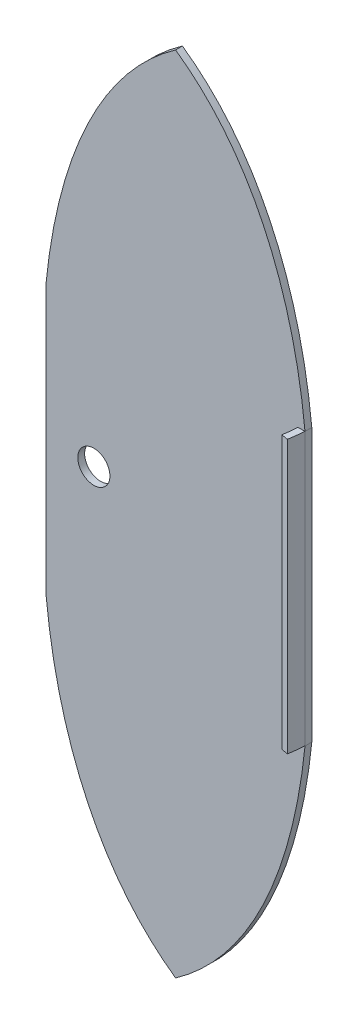
SolidWorks part; units mm, degrees
material "1060 Alloy"
ref_plane "Front Plane" through (0, 0, 0) normal (0, 0, 1) x (1, 0, 0)
ref_plane "Top Plane" through (0, 0, 0) normal (0, 1, 0) x (1, 0, 0)
ref_plane "Right Plane" through (0, 0, 0) normal (1, 0, 0) x (0, 0, -1)
sketch "Sketch1" plane through (0, 0, 0) normal (0, 0, 1) x (1, 0, 0)
  line L2 (0, 0) -> (-130.3555, 0) construction
  line L3 (0, 0) -> (0, -49.0041) construction
  line L4 (-48.26, 0) -> (-48.26, -101.6)
  line L7 (48.26, 0) -> (48.26, -101.6)
  line L8 (0, -50.8) -> (-48.26, -50.8) construction
  line L9 (48.26, 0) -> (45.72, 0)
  line L10 (45.72, 0) -> (45.72, -101.6)
  line L11 (45.72, -101.6) -> (48.26, -101.6)
  circle A0 centre (-30.48, -50.8) radius 5.9944
  spline S0 degree 3 poles (-48.26, 0) (-44.5897, 36.5514) (-31.4093, 76.9608) (0, 99.06) knots 0 0 0 0 1 1 1 1
  spline S1 degree 3 poles (48.26, 0) (44.5897, 36.5514) (31.4093, 76.9608) (0, 99.06) knots 0 0 0 0 1 1 1 1
  spline S2 degree 3 poles (48.26, -101.6) (44.5897, -138.1514) (31.4093, -178.5608) (0, -200.66) knots 0 0 0 0 1 1 1 1
  spline S3 degree 3 poles (-48.26, -101.6) (-44.5897, -138.1514) (-31.4093, -178.5608) (0, -200.66) knots 0 0 0 0 1 1 1 1
  dimension "D2" = 2.54
  dimension "D3" = 101.6
  dimension "D4" = 18.2437
  dimension "D5" = 45.72
  dimension "D6" = 18.2437
  dimension "D7" = 99.06
  dimension "D8" = 40.7518
  dimension "D9" = 139.7535
  dimension "D10" = 38.1535
  dimension "D12" = 81.9693
extrude "Boss-Extrude1" add sketch "Sketch1" along normal blind 2.54 contours L10 L11 L7 L9 | L4 S3 S2 L11 L10 L9 S1 S0 region at (-0.3862, -50.8, 0) region at (46.99, -50.8, 0)
revolve "Revolve3" add sketch "Sketch1<5>" angle 10 about L3 region at (46.99, -50.8, 0)
sketch "Sketch1<5>" plane through (0, 0, 0) normal (0, 0, 1) x (1, 0, 0) same geometry as "Sketch1"
